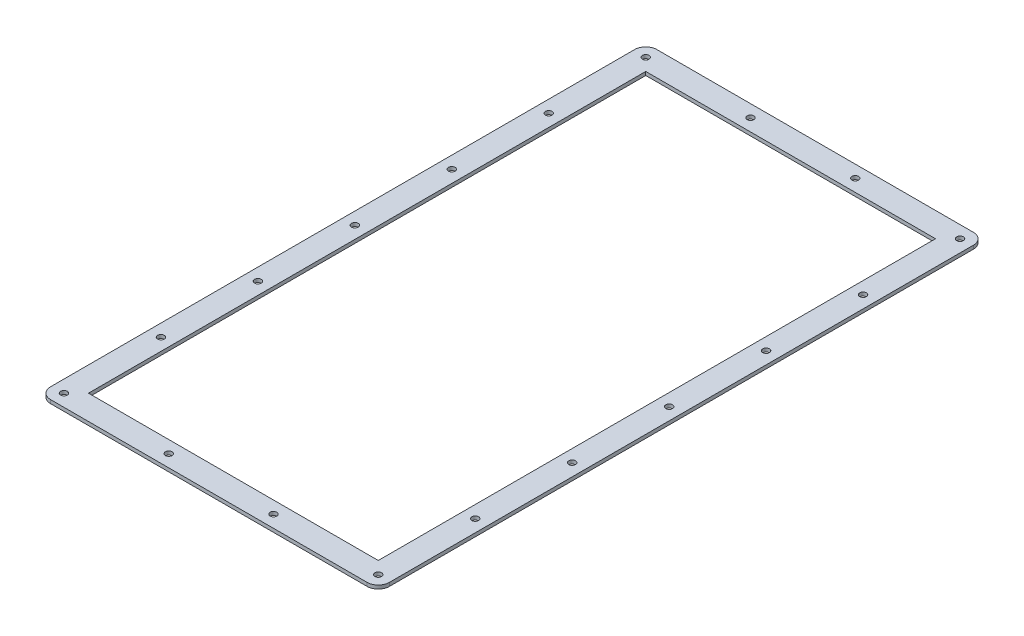
SolidWorks part; units mm, degrees
material "5052-H32"
ref_plane "Front Plane" through (0, 0, 0) normal (0, 0, 1) x (1, 0, 0)
ref_plane "Top Plane" through (0, 0, 0) normal (0, 1, 0) x (1, 0, 0)
ref_plane "Right Plane" through (0, 0, 0) normal (1, 0, 0) x (0, 0, -1)
sketch "Sketch1" plane through (0, 0, 0) normal (0, 1, 0) x (1, 0, 0)
  line L0 (-152, 272) -> (152, 272)
  line L1 (-130, -250) -> (130, -250)
  line L2 (-130, -250) -> (-130, 250)
  line L3 (-130, 250) -> (130, 250)
  line L4 (130, -250) -> (130, 250)
  line L5 (-130, -250) -> (130, 250) construction
  line L6 (-130, 250) -> (130, -250) construction
  line L7 (152, -272) -> (152, 272)
  line L8 (-152, -272) -> (152, -272)
  line L9 (-152, -272) -> (-152, 272)
  line L12 (130, 0) -> (-130, 0) construction
  circle A34 centre (141, 261) radius 3
  circle A35 centre (47, 261) radius 3
  circle A36 centre (-47, 261) radius 3
  circle A37 centre (-141, 261) radius 3
  circle A90 centre (141, 174) radius 3
  circle A91 centre (141, 87) radius 3
  circle A92 centre (141, 0) radius 3
  circle A93 centre (141, -87) radius 3
  circle A94 centre (141, -174) radius 3
  circle A102 centre (-141, 174) radius 3
  circle A103 centre (141, -261) radius 3
  circle A106 centre (-141, 87) radius 3
  circle A107 centre (47, -261) radius 3
  circle A110 centre (-141, 0) radius 3
  circle A111 centre (-47, -261) radius 3
  circle A114 centre (-141, -87) radius 3
  circle A115 centre (-141, -261) radius 3
  circle A118 centre (-141, -174) radius 3
  circle A119 centre (47, -87) radius 3 [skipped]
  circle A120 centre (-47, -87) radius 3 [skipped]
  circle A121 centre (47, 174) radius 3 [skipped]
  circle A122 centre (-47, 174) radius 3 [skipped]
  circle A123 centre (47, 87) radius 3 [skipped]
  circle A124 centre (47, 0) radius 3 [skipped]
  circle A125 centre (-47, 0) radius 3 [skipped]
  circle A126 centre (-47, 87) radius 3 [skipped]
  circle A127 centre (47, -174) radius 3 [skipped]
  circle A128 centre (-47, -174) radius 3 [skipped]
  dimension "D4" = 6
  dimension "D2" = 500
  dimension "D1" = 22
  dimension "D3" = 260
  dimension "D5" = 11
  dimension "D6" = 11
  dimension "D9" = 87
  dimension "D10" = 94
  dimension "D7" = 4
  dimension "D8" = 7
extrude "Boss-Extrude1" add sketch "Sketch1" along normal blind 3.175 contours L9 L8 L7 L0 L4 L1 L2 L3 A34 region at (0, 0, -265.7682)
fillet "Fillet1" radius 10 4 edges at (152, 1.5875, 272) (-152, 1.5875, 272) (152, 1.5875, -272) (-152, 1.5875, -272)
equation "\"L\"= 500"
equation "\"W\"= 260"
equation "\"H\"= 110"
equation "\"Compartment Width\"= 90"
equation "\"T\"= 4.7625 * 2 / 3"
equation "\"Inside Fillet Radius\"= 5.55625"
equation "\"Hole\"=15"
equation "\"D2@Sketch1\"=\"L\""
equation "\"D1@Boss-Extrude1\"=\"T\""
equation "\"D3@Sketch1\"=\"W\""
equation "\"D9@Sketch1\"=(\"L\"+22)/6"
equation "\"D10@Sketch1\"=(\"W\"+22)/3"
